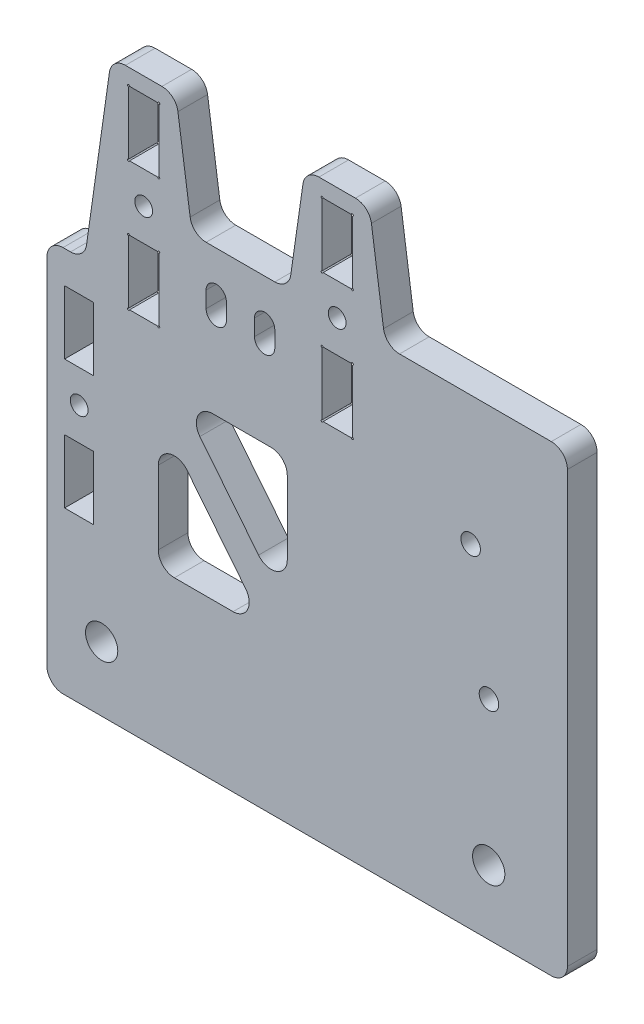
SolidWorks part; units mm, degrees
ref_plane "Front Plane" through (0, 0, 0) normal (0, 0, 1) x (1, 0, 0)
ref_plane "Top Plane" through (0, 0, 0) normal (0, 1, 0) x (1, 0, 0)
ref_plane "Right Plane" through (0, 0, 0) normal (1, 0, 0) x (0, 0, -1)
sketch "Sketch1" plane through (0, 0, 0) normal (0, 0, 1) x (1, 0, 0)
  line L0 (-40.2246, 5.8803) -> (-40.2246, -38.4697) construction
  line L1 (51.8504, -38.4697) -> (-46.5746, -38.4697)
  line L3 (-46.5746, 34.5553) -> (-46.5746, 52.6159)
  line L4 (-46.5746, -38.4697) -> (-46.5746, 34.5553)
  line L5 (51.8504, -38.4697) -> (-46.5746, 34.5553) construction
  line L6 (42.1271, 34.7961) -> (-46.5746, -38.4697) construction
  line L7 (-43.0956, -6.6197) -> (-37.3536, -6.6197)
  line L8 (-43.0956, 18.7803) -> (-37.3536, 18.7803)
  line L9 (-43.0956, 18.7803) -> (-43.0956, 31.2803)
  line L10 (-43.0956, 31.2803) -> (-37.3536, 31.2803)
  line L11 (-37.3536, 18.7803) -> (-37.3536, 31.2803)
  line L12 (-43.0956, 18.7803) -> (-37.3536, 31.2803) construction
  line L13 (-43.0956, 31.2803) -> (-37.3536, 18.7803) construction
  line L14 (-43.0956, -6.6197) -> (-43.0956, 5.8803)
  line L15 (-43.0956, 5.8803) -> (-37.3536, 5.8803)
  line L16 (-37.3536, -6.6197) -> (-37.3536, 5.8803)
  line L17 (-43.0956, -6.6197) -> (-37.3536, 5.8803) construction
  line L18 (-43.0956, 5.8803) -> (-37.3536, -6.6197) construction
  line L19 (-46.5746, 52.6159) -> (51.8504, 52.6159)
  line L20 (51.8504, -25.7697) -> (-46.5746, -25.7697) construction
  line L21 (-40.2246, -0.3697) -> (-40.2246, 25.0303) construction
  line L24 (51.8504, 52.6159) -> (55.8972, 52.6159)
  line L26 (51.8504, -38.4697) -> (55.8972, -38.4697)
  line L27 (55.8972, 52.6159) -> (55.8972, -38.4697)
  circle A0 centre (-35.7968, -25.7697) radius 3.175
  circle A1 centre (40.4032, -25.7697) radius 3.175
  circle A2 centre (-40.2246, 12.3303) radius 1.7526
  point P0 (0, 0)
  point P8 (-40.2246, 25.0303)
  point P14 (-40.2246, -0.3697)
  dimension "D10" = 6.35
  dimension "D13" = 3.5052
  dimension "D1" = 98.425
  dimension "D2" = 73.025
  dimension "D3" = 5.742
  dimension "D4" = 12.5
  dimension "D6" = 6.35
  dimension "D7" = 18.0606
  dimension "D8" = 15.494
  dimension "D12" = 10.7778
  dimension "D5" = 2
  dimension "D11" = 2
extrude "Boss-Extrude1" add sketch "Sketch1" along normal blind 5.842
sketch "Sketch2" plane through (0, 0, 5.842) normal (0, 0, 1) x (1, 0, 0)
  line L0 (55.8972, -38.4697) -> (55.8972, 52.6159) construction
  line L1 (-46.5746, -38.4697) -> (55.8972, -38.4697) construction
  line L2 (33.2912, 44.7153) -> (43.1972, 44.7153) construction
  line L3 (33.2912, -3.5447) -> (43.1972, -3.5447) construction
  line L4 (38.2442, -3.5447) -> (38.2442, 44.7153) construction
  line L6 (48.0747, 0.1423) -> (28.4136, 0.1423)
  line L7 (48.2732, 0.3408) -> (48.2732, 40.8299)
  line L8 (48.0747, 41.0283) -> (28.4136, 41.0283)
  line L9 (28.2152, 0.3408) -> (28.2152, 40.8299)
  line L10 (48.2732, 0.1423) -> (28.2152, 41.0283) construction
  line L11 (48.2732, 41.0283) -> (28.2152, 0.1423) construction
  circle A0 centre (43.1972, -3.5447) radius 1.7526
  circle A1 centre (33.2912, -3.5447) radius 1.7526
  circle A2 centre (43.1972, 44.7153) radius 1.7526
  circle A3 centre (33.2912, 44.7153) radius 1.7526
  arc A4 (48.0747, 0.1423) -> (48.2732, 0.3408) centre (48.2732, 0.1423) ccw
  arc A5 (48.2732, 40.8299) -> (48.0747, 41.0283) centre (48.2732, 41.0283) ccw
  arc A6 (28.2152, 40.8299) -> (28.4136, 41.0283) centre (28.2152, 41.0283) cw
  arc A7 (28.4136, 0.1423) -> (28.2152, 0.3408) centre (28.2152, 0.1423) cw
  point P14 (38.2442, 20.5853)
  dimension "D1" = 3.5052
  dimension "D6" = 0.3969
  dimension "D7" = 0.3969
  dimension "D2" = 12.7
  dimension "D3" = 34.925
  dimension "D4" = 20.058
  dimension "D5" = 40.886
extrude "Cut-Extrude1" [suppressed] cut sketch "Sketch2" against normal through all
sketch "Sketch3" plane through (0, 0, 5.842) normal (0, 0, 1) x (1, 0, 0)
  line L0 (-46.5746, 39.9159) -> (55.8972, 39.9159) construction
  line L1 (-46.5746, 52.6159) -> (-46.5746, -38.4697) construction
  line L2 (55.8972, -38.4697) -> (55.8972, 52.6159) construction
  line L3 (55.8972, 52.6159) -> (-46.5746, 52.6159) construction
  line L4 (7.5909, 46.2659) -> (13.5599, 33.5659) construction
  line L5 (-24.7385, 33.5659) -> (-30.3106, 33.5659)
  line L6 (-24.5401, 33.7644) -> (-24.5401, 46.0675)
  line L7 (-24.7385, 46.2659) -> (-30.3106, 46.2659)
  line L8 (-30.5091, 33.7644) -> (-30.5091, 46.0675)
  line L9 (-24.5401, 33.5659) -> (-30.5091, 46.2659) construction
  line L10 (-8.4746, 52.6159) -> (-8.4746, 39.9159) construction
  line L11 (-24.5401, 46.2659) -> (-30.5091, 33.5659) construction
  line L12 (7.5909, 33.5659) -> (13.5599, 46.2659) construction
  line L13 (13.5599, 33.7644) -> (13.5599, 46.0675)
  line L14 (7.7894, 46.2659) -> (13.3615, 46.2659)
  line L15 (7.5909, 33.7644) -> (7.5909, 46.0675)
  line L16 (7.7894, 33.5659) -> (13.3615, 33.5659)
  arc A0 (-24.7385, 33.5659) -> (-24.5401, 33.7644) centre (-24.5401, 33.5659) ccw
  arc A1 (-30.5091, 33.7644) -> (-30.3106, 33.5659) centre (-30.5091, 33.5659) ccw
  arc A2 (-24.7385, 46.2659) -> (-24.5401, 46.0675) centre (-24.5401, 46.2659) cw
  arc A3 (-30.5091, 46.0675) -> (-30.3106, 46.2659) centre (-30.5091, 46.2659) cw
  arc A4 (13.5599, 46.0675) -> (13.3615, 46.2659) centre (13.5599, 46.2659) ccw
  arc A5 (7.7894, 46.2659) -> (7.5909, 46.0675) centre (7.5909, 46.2659) ccw
  arc A6 (13.5599, 33.7644) -> (13.3615, 33.5659) centre (13.5599, 33.5659) cw
  arc A7 (7.7894, 33.5659) -> (7.5909, 33.7644) centre (7.5909, 33.5659) cw
  point P6 (-27.5246, 39.9159)
  point P7 (-27.5246, 39.9159)
  point P39 (10.5754, 39.9159)
  dimension "D3" = 0.3969
  dimension "D4" = 0.3969
  dimension "D1" = 5.969
  dimension "D2" = 12.7
  dimension "D5" = 12.7
  dimension "D6" = 19.05
  dimension "D9" = 19.05
extrude "Cut-Extrude2" cut sketch "Sketch3" against normal through all
sketch "Sketch4" plane through (0, 0, 5.842) normal (0, 0, 1) x (1, 0, 0)
  line L0 (-30.5091, 39.9159) -> (13.5599, 39.9159) construction
  line L3 (10.5754, 39.9159) -> (10.5754, 65.3159) construction
  line L4 (-8.4746, 39.9159) -> (-8.4746, 46.2659) construction
  line L5 (1.0366, 52.6159) -> (4.2254, 74.8409)
  line L6 (13.3615, 71.6659) -> (7.7894, 71.6659)
  line L7 (13.5599, 71.4675) -> (13.5599, 59.1644)
  line L8 (13.3615, 58.9659) -> (7.7894, 58.9659)
  line L9 (7.5909, 71.4675) -> (7.5909, 59.1644)
  line L10 (13.5599, 71.6659) -> (7.5909, 58.9659) construction
  line L11 (13.5599, 58.9659) -> (7.5909, 71.6659) construction
  line L12 (55.8972, 52.6159) -> (-46.5746, 52.6159) construction
  line L13 (4.2254, 74.8409) -> (16.9254, 74.8409)
  line L14 (16.9254, 74.8409) -> (20.0866, 52.6159)
  line L15 (20.0866, 52.6159) -> (1.0366, 52.6159)
  line L16 (-30.5091, 58.9659) -> (-24.5401, 71.6659) construction
  line L17 (-30.5091, 71.6659) -> (-24.5401, 58.9659) construction
  line L18 (-37.0358, 52.6159) -> (-17.9858, 52.6159)
  line L19 (-33.8746, 74.8409) -> (-37.0358, 52.6159)
  line L20 (-21.1746, 74.8409) -> (-33.8746, 74.8409)
  line L21 (-24.5401, 71.4675) -> (-24.5401, 59.1644)
  line L22 (-30.3106, 58.9659) -> (-24.7385, 58.9659)
  line L23 (-30.5091, 71.4675) -> (-30.5091, 59.1644)
  line L24 (-30.3106, 71.6659) -> (-24.7385, 71.6659)
  line L25 (-17.9858, 52.6159) -> (-21.1746, 74.8409)
  line L26 (13.5599, 33.7644) -> (13.5599, 46.0675) construction
  line L27 (-30.5091, 46.0675) -> (-30.5091, 33.7644) construction
  arc A0 (13.5599, 71.4675) -> (13.3615, 71.6659) centre (13.5599, 71.6659) ccw
  arc A1 (13.3615, 58.9659) -> (13.5599, 59.1644) centre (13.5599, 58.9659) ccw
  arc A2 (7.7894, 58.9659) -> (7.5909, 59.1644) centre (7.5909, 58.9659) cw
  arc A3 (7.5909, 71.4675) -> (7.7894, 71.6659) centre (7.5909, 71.6659) cw
  arc A4 (-24.5401, 71.4675) -> (-24.7385, 71.6659) centre (-24.5401, 71.6659) ccw
  arc A5 (-30.5091, 71.4675) -> (-30.3106, 71.6659) centre (-30.5091, 71.6659) cw
  arc A6 (-24.7385, 58.9659) -> (-24.5401, 59.1644) centre (-24.5401, 58.9659) ccw
  arc A7 (-30.3106, 58.9659) -> (-30.5091, 59.1644) centre (-30.5091, 58.9659) cw
  point P20 (10.5754, 74.8409)
  point P29 (-27.5246, 74.8409)
  dimension "D7" = 0.3969
  dimension "D8" = 0.3969
  dimension "D1" = 25.4
  dimension "D2" = 12.7
  dimension "D3" = 5.969
  dimension "D4" = 9.525
  dimension "D5" = 12.7
  dimension "D6" = 19.05
extrude "Boss-Extrude2" add sketch "Sketch4" against normal up to surface (5.842 mm away) up to face at (10.5754, 39.9159, 0)
fillet "Fillet1" radius 3.175 7 edges at (16.9254, 74.8409, 2.921) (4.2254, 74.8409, 2.921) (-17.9858, 52.6159, 2.921) (-21.1746, 74.8409, 2.921) (-33.8746, 74.8409, 2.921)
sketch "Sketch5" plane through (0, 0, 5.842) normal (0, 0, 1) x (1, 0, 0)
  line L0 (-27.5246, 71.6659) -> (-27.5246, 33.5659) construction
  line L1 (-24.7385, 71.6659) -> (-30.3106, 71.6659) construction
  line L2 (-30.3106, 33.5659) -> (-24.7385, 33.5659) construction
  line L3 (10.5754, 71.6659) -> (10.5754, 33.5659) construction
  line L4 (13.3615, 71.6659) -> (7.7894, 71.6659) construction
  line L5 (7.7894, 33.5659) -> (13.3615, 33.5659) construction
  circle A0 centre (-27.5246, 52.6159) radius 1.7526
  circle A1 centre (10.5754, 52.6159) radius 1.7526
  dimension "D1" = 3.5052
  dimension "D2" = 3.5052
extrude "Cut-Extrude3" cut sketch "Sketch5" against normal through all
sketch "Sketch6" plane through (0, 0, 5.842) normal (0, 0, 1) x (1, 0, 0)
  line L0 (-37.0358, 52.6159) -> (-39.1672, 37.6303)
  line L1 (-34.2626, 72.113) -> (-37.0358, 52.6159) construction
  line L2 (-37.3536, 31.2803) -> (-43.0956, 31.2803) construction
  line L3 (-39.1672, 37.6303) -> (-46.5746, 37.6303)
  line L4 (-46.5746, 52.6159) -> (-46.5746, -38.4697) construction
  line L5 (-46.5746, 37.6303) -> (-46.5746, 52.6159)
  line L6 (-46.5746, 52.6159) -> (-37.0358, 52.6159)
  dimension "D1" = 6.35
extrude "Cut-Extrude4" cut sketch "Sketch6" against normal through all
fillet "Fillet2" radius 3.175 5 edges at (-39.1672, 37.6303, 2.921) (-46.5746, 37.6303, 2.921) (-46.5746, -38.4697, 2.921) (55.8972, 52.6159, 2.921) (55.8972, -38.4697, 2.921)
sketch "Sketch7" [suppressed] plane through (0, 0, 5.842) normal (0, 0, 1) x (1, 0, 0)
  line L0 (6.4764, -22.5947) -> (19.1764, -22.5947) construction
  line L1 (6.4764, -19.4197) -> (19.1764, -19.4197)
  line L2 (6.4764, -25.7697) -> (19.1764, -25.7697)
  line L3 (-43.3996, -38.4697) -> (52.7222, -38.4697) construction
  arc A0 (6.4764, -19.4197) -> (6.4764, -25.7697) centre (6.4764, -22.5947) ccw
  arc A1 (19.1764, -25.7697) -> (19.1764, -19.4197) centre (19.1764, -22.5947) ccw
  point P2 (12.8264, -22.5947)
  dimension "D3" = 3.175
  dimension "D1" = 12.7
  dimension "D2" = 12.7
extrude "Cut-Extrude5" [suppressed] cut sketch "Sketch7" against normal through all
sketch "Sketch8" [suppressed] plane through (0, 0, 5.842) normal (0, 0, 1) x (1, 0, 0)
  line L0 (17.7972, -38.4697) -> (17.7972, 37.7303) construction
  line L1 (-43.3996, -38.4697) -> (52.7222, -38.4697) construction
  line L2 (55.8972, -35.2947) -> (55.8972, 49.4409) construction
  line L3 (14.6222, 5.9803) -> (20.9722, 5.9803) construction
  line L4 (14.6222, 7.5678) -> (20.9722, 7.5678)
  line L5 (14.6222, 4.3928) -> (20.9722, 4.3928)
  line L6 (14.6222, 25.0303) -> (20.9722, 25.0303) construction
  line L7 (14.6222, 26.6178) -> (20.9722, 26.6178)
  line L8 (14.6222, 23.4428) -> (20.9722, 23.4428)
  arc A0 (14.6222, 7.5678) -> (14.6222, 4.3928) centre (14.6222, 5.9803) ccw
  arc A1 (20.9722, 4.3928) -> (20.9722, 7.5678) centre (20.9722, 5.9803) ccw
  arc A2 (14.6222, 26.6178) -> (14.6222, 23.4428) centre (14.6222, 25.0303) ccw
  arc A3 (20.9722, 23.4428) -> (20.9722, 26.6178) centre (20.9722, 25.0303) ccw
  point P8 (17.7972, 5.9803)
  point P17 (17.7972, 25.0303)
  dimension "D2" = 1.5875
  dimension "D1" = 38.1
  dimension "D3" = 6.35
  dimension "D4" = 76.2
  dimension "D5" = 2
  dimension "D6" = 44.45
extrude "Cut-Extrude6" [suppressed] cut sketch "Sketch8" against normal through all
sketch "Sketch9" [suppressed] plane through (0, 0, 5.842) normal (0, 0, 1) x (1, 0, 0)
  line L0 (3.3014, -22.5947) -> (-46.5746, -22.5947) construction
  line L1 (-46.5746, 34.4553) -> (-46.5746, -35.2947) construction
  line L2 (-15.7486, -25.7697) -> (-15.7486, -19.4197) construction
  line L3 (-17.3361, -25.7697) -> (-17.3361, -19.4197)
  line L4 (-14.1611, -25.7697) -> (-14.1611, -19.4197)
  line L5 (-3.0486, -25.7697) -> (-3.0486, -19.4197) construction
  line L6 (-4.6361, -25.7697) -> (-4.6361, -19.4197)
  line L7 (-1.4611, -25.7697) -> (-1.4611, -19.4197)
  arc A0 (6.4764, -19.4197) -> (6.4764, -25.7697) centre (6.4764, -22.5947) ccw construction
  arc A1 (-17.3361, -25.7697) -> (-14.1611, -25.7697) centre (-15.7486, -25.7697) ccw
  arc A2 (-14.1611, -19.4197) -> (-17.3361, -19.4197) centre (-15.7486, -19.4197) ccw
  arc A3 (-4.6361, -25.7697) -> (-1.4611, -25.7697) centre (-3.0486, -25.7697) ccw
  arc A4 (-1.4611, -19.4197) -> (-4.6361, -19.4197) centre (-3.0486, -19.4197) ccw
  point P10 (-15.7486, -22.5947)
  point P18 (-3.0486, -22.5947)
  dimension "D2" = 1.5875
  dimension "D1" = 6.35
  dimension "D3" = 19.05
extrude "Cut-Extrude7" [suppressed] cut sketch "Sketch9" against normal through all
sketch "Sketch10" plane through (0, 0, 5.842) normal (0, 0, 1) x (1, 0, 0)
  line L0 (-20.5876, 24.0409) -> (0.7464, 24.0409)
  line L1 (-30.3106, 33.5659) -> (-24.7385, 33.5659) construction
  line L2 (-24.6536, 18.9584) -> (-24.6536, -7.7091)
  line L3 (-37.3536, 18.7803) -> (-37.3536, 31.2803) construction
  line L4 (0.7464, 24.0409) -> (0.7464, -2.6266)
  line L5 (-3.3196, -7.7091) -> (-24.6536, -7.7091)
  line L7 (-24.6536, 18.9584) -> (-3.3196, -7.7091)
  line L8 (-20.5876, 24.0409) -> (0.7464, -2.6266)
  dimension "D1" = 9.525
  dimension "D2" = 12.7
extrude "Cut-Extrude8" cut sketch "Sketch10" against normal through all
fillet "Fillet3" radius 3.175 6 edges at (0.7464, 24.0409, 2.921) (0.7464, -2.6266, 2.921) (-20.5876, 24.0409, 2.921) (-24.6536, 18.9584, 2.921) (-24.6536, -7.7091, 2.921) (-3.3196, -7.7091, 2.921)
sketch "Sketch11" plane through (0, 0, 5.842) normal (0, 0, 1) x (1, 0, 0)
  line L0 (55.8972, -35.2947) -> (55.8972, 49.4409) construction
  line L1 (52.7222, 52.6159) -> (22.842, 52.6159) construction
  circle A0 centre (36.8472, 27.2159) radius 1.92
  circle A1 centre (40.4472, 2.5659) radius 1.92
  dimension "D1" = 3.84
  dimension "D2" = 3.84
  dimension "D3" = 3.6
  dimension "D4" = 24.65
  dimension "D5" = 19.05
  dimension "D6" = 25.4
extrude "Cut-Extrude9" cut sketch "Sketch11" against normal through all
sketch "Sketch12" plane through (0, 0, 5.842) normal (0, 0, 1) x (1, 0, 0)
  line L0 (-24.5401, 42.8787) -> (7.5909, 42.8787) construction
  line L1 (-24.5401, 33.7644) -> (-24.5401, 46.0675) construction
  line L2 (7.5909, 46.0675) -> (7.5909, 33.7644) construction
  line L3 (-8.4746, 52.6159) -> (-8.4746, 42.8787) construction
  line L4 (-1.7153, 52.6159) -> (-15.2338, 52.6159) construction
  line L5 (-3.7121, 41.2912) -> (-3.7121, 44.4662) construction
  line L6 (-5.7121, 41.2912) -> (-5.7121, 44.4662)
  line L7 (-1.7121, 41.2912) -> (-1.7121, 44.4662)
  line L8 (-13.2371, 41.2912) -> (-13.2371, 44.4662) construction
  line L9 (-11.2371, 41.2912) -> (-11.2371, 44.4662)
  line L10 (-15.2371, 41.2912) -> (-15.2371, 44.4662)
  arc A0 (-5.7121, 41.2912) -> (-1.7121, 41.2912) centre (-3.7121, 41.2912) ccw
  arc A1 (-1.7121, 44.4662) -> (-5.7121, 44.4662) centre (-3.7121, 44.4662) ccw
  arc A2 (-11.2371, 41.2912) -> (-15.2371, 41.2912) centre (-13.2371, 41.2912) cw
  arc A3 (-15.2371, 44.4662) -> (-11.2371, 44.4662) centre (-13.2371, 44.4662) cw
  point P12 (-3.7121, 42.8787)
  point P19 (-13.2371, 42.8787)
  dimension "D2" = 2
  dimension "D1" = 3.175
  dimension "D3" = 4.7625
extrude "Cut-Extrude10" cut sketch "Sketch12" against normal through all
